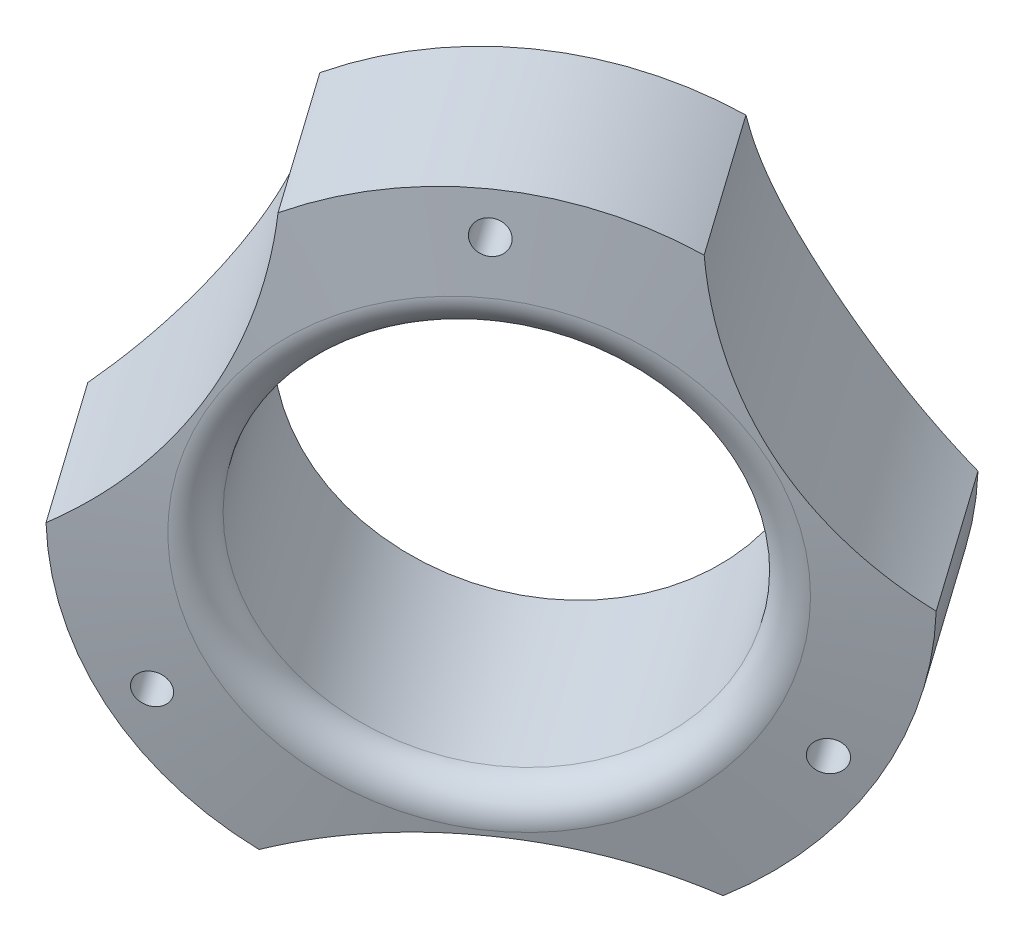
SolidWorks part; units mm, degrees
material "ABS"
ref_plane "前视基准面" through (0, 0, 0) normal (0, 0, 1) x (1, 0, 0)
ref_plane "上视基准面" through (0, 0, 0) normal (0, 1, 0) x (1, 0, 0)
ref_plane "右视基准面" through (0, 0, 0) normal (1, 0, 0) x (0, 0, -1)
other "Configuration Table"
sketch "草图1" plane through (0, 0, 0) normal (0, 1, 0) x (1, 0, 0)
  line L0 (0, 0) -> (50000, 0) construction
  line L1 (0, 0) -> (43301.2702, 25000) construction
  line L2 (0, 0) -> (25000, 43301.2702) construction
  line L3 (0, 0) -> (0, 50000) construction
  line L4 (0, 0) -> (-25000, 43301.2702) construction
  line L5 (0, 0) -> (-43301.2702, 25000) construction
  line L6 (17.4332, 10.0651) -> (35.1224, 20.2779)
  line L7 (35.1224, 20.2779) -> (22.2401, 38.5209)
  line L8 (22.2401, 38.5209) -> (11.039, 19.1201)
  line L9 (11.039, 19.1201) -> (17.4332, 10.0651)
  line L10 (29.4107, 28.3665) -> (21.242, 22.5982) construction
  line L11 (21.242, 22.5982) -> (26.426, 15.257)
  line L12 (21.242, 22.5982) -> (16.7334, 28.983)
  spline S0 degree 4 poles (4.5441, -13.9852) (5.069, -13.9115) (6.1117, -13.7144) (7.5966, -13.2868) (9.4525, -12.4738) (11.1485, -11.4611) (12.673, -10.2854) (14.0902, -8.9027) (15.2006, -7.528) (16.0517, -6.2294) (16.6357, -5.1571) (16.9969, -4.4036) (17.2795, -3.7437) (17.4701, -3.2541) (17.647, -2.7595) (17.7869, -2.3315) (17.8956, -1.9726) (17.9965, -1.6106) (18.0724, -1.3201) (18.1431, -1.0312) (18.201, -0.7763) (18.2495, -0.5466) (18.2961, -0.3139) (18.338, -0.0934) (18.3688, 0.0809) (18.404, 0.2961) (18.438, 0.517) (18.4698, 0.7375) (18.5019, 0.9839) (18.5336, 1.2626) (18.5616, 1.5443) (18.5855, 1.8273) (18.6051, 2.1103) (18.6204, 2.3933) (18.6344, 2.7474) (18.6427, 3.1726) (18.6402, 3.6687) (18.606, 4.6606) (18.4743, 6.0736) (18.1443, 7.891) (17.4882, 10.0676) (16.5951, 12.1579) (15.4804, 14.1385) (14.1536, 15.9992) (12.6297, 17.7192) (10.7951, 19.3989) (8.6272, 20.9716) (6.1287, 22.3558) (3.3088, 23.4722) (0.3713, 24.2251) (-2.6362, 24.611) (-5.6679, 24.6319) (-8.6804, 24.2953) (-11.6337, 23.6131) (-14.4905, 22.6011) (-17.8988, 20.9477) (-21.6682, 18.3857) (-25.4815, 14.66) (-28.8831, 9.6089) (-31.2279, 3.9916) (-32.5355, -2.3024) (-32.5832, -9.4982) (-30.886, -17.2942) (-27.0418, -25.1548) (-21.1423, -32.1629) (-13.78, -37.6027) (-5.394, -41.2569) (3.5764, -43.0207) (12.7127, -42.8868) (21.6333, -40.9289) (30.0036, -37.2857) (37.5425, -32.1439) (44.0239, -25.7248) (49.277, -18.2707) (53.1837, -10.0336) (55.6748, -1.2666) (56.7255, 7.7843) (56.3496, 16.8863) (54.5948, 25.8236) (51.5367, 34.4007) (47.2736, 42.4454) (41.6252, 50.2165) (33.2939, 58.6988) (21.6024, 66.7973) (6.2316, 72.9489) (-11.9297, 75.3897) (-30.1426, 73.5037) (-47.4501, 67.5662) (-63.0493, 58.0235) (-76.3038, 45.4399) (-86.7456, 30.4509) (-94.067, 13.7235) (-98.1075, -4.0757) (-98.837, -22.3066) (-96.337, -40.374) (-90.7813, -57.741) (-82.4178, -73.9383) (-71.5503, -88.568) (-58.5225, -101.306) (-43.7037, -111.9004) (-27.476, -120.169) (-10.2235, -125.9948) (7.6766, -129.3207) (25.8616, -130.1437) (43.989, -128.5088) (59.522, -125.003) (72.4202, -120.5917) (82.8104, -116.0253) (90.8771, -111.8583) (98.6697, -107.1992) (106.1617, -102.071) (114.2246, -95.801) (122.6763, -88.2215) (131.2888, -79.1727) (139.0767, -69.4058) (144.8157, -60.9536) (149.48, -53.1674) (153.2371, -46.1706) (156.1751, -40.0285) (158.8259, -33.7588) (160.8418, -28.4575) (162.3378, -24.1741) (163.5443, -20.3917) (164.5049, -17.1274) (165.2564, -14.393) (165.828, -12.1982) (166.3703, -9.9944) (166.8184, -8.0627) (167.1848, -6.398) (167.4765, -5.0161) (167.7053, -3.8925) (167.892, -2.9476) (168.0629, -2.0497) (168.1956, -1.3461) (168.4043, -0.1916) (168.4882, 0.2863) (168.6688, 1.3366) (168.7622, 1.9047) (168.8711, 2.5704) (169.0198, 3.5044) (169.1948, 4.6573) (169.389, 6.0027) (169.5701, 7.3351) (169.7422, 8.6768) (169.9433, 10.3507) (170.1641, 12.3645) (170.391, 14.7154) (170.6086, 17.4069) (170.7844, 20.1009) (170.9186, 22.7976) (171.0111, 25.4959) (171.0621, 28.1953) (171.0718, 30.8952) (171.0401, 33.595) (170.9491, 36.9686) (170.6302, 43.7113) (169.6923, 53.7988) (167.722, 65.8035) (165.138, 76.2991) (163.208, 82.7681) (162.3863, 85.3399) knots 0 0 0 0 0 0.002183 0.004365 0.006343 0.00832 0.010298 0.012275 0.014479 0.01558 0.016682 0.0173 0.017918 0.018536 0.018845 0.019463 0.019772 0.020081 0.02039 0.020699 0.021008 0.021162 0.021317 0.021626 0.021918 0.022064 0.02221 0.022501 0.022793 0.023085 0.023377 0.023669 0.023961 0.024253 0.024544 0.025128 0.025712 0.026296 0.028631 0.030966 0.033302 0.035637 0.037972 0.040307 0.042695 0.045083 0.048197 0.05131 0.054424 0.057538 0.060652 0.063766 0.066879 0.069993 0.073107 0.07622 0.082448 0.088676 0.094903 0.10113 0.107357 0.114993 0.124334 0.133675 0.143016 0.152357 0.161699 0.17104 0.18038 0.189722 0.199063 0.208404 0.217745 0.227086 0.236427 0.245769 0.25511 0.264451 0.273792 0.283133 0.292474 0.301815 0.313225 0.331907 0.35059 0.369272 0.387954 0.406636 0.425318 0.444001 0.462683 0.481365 0.500047 0.518729 0.537412 0.556094 0.574776 0.593458 0.612141 0.630823 0.649505 0.668187 0.68687 0.705552 0.724234 0.742916 0.752258 0.761599 0.77094 0.780281 0.789622 0.798963 0.812975 0.826987 0.840998 0.85034 0.85501 0.864351 0.873692 0.878363 0.883033 0.887704 0.892374 0.89471 0.897045 0.89938 0.901716 0.904051 0.905219 0.906387 0.907554 0.908722 0.909306 0.90989 0.911057 0.912447 0.912794 0.913142 0.913837 0.915226 0.916616 0.918006 0.919396 0.920785 0.922175 0.924955 0.927734 0.930513 0.933293 0.936072 0.938852 0.941631 0.944411 0.94719 0.94997 0.955529 0.972205 0.988882 1 1 1 1 1 construction
  spline S1 degree 4 poles (18.3541, 0) (18.3651, 0.0621) (18.381, 0.1554) (18.404, 0.2961) (18.438, 0.517) (18.4698, 0.7375) (18.5019, 0.9839) (18.5336, 1.2626) (18.5616, 1.5443) (18.5855, 1.8273) (18.6051, 2.1103) (18.6204, 2.3933) (18.6344, 2.7474) (18.6427, 3.1726) (18.6402, 3.6687) (18.606, 4.6606) (18.4743, 6.0736) (18.1443, 7.891) (17.4882, 10.0676) (16.5951, 12.1579) (15.4804, 14.1385) (14.1536, 15.9992) (12.6297, 17.7192) (10.7951, 19.3989) (8.6272, 20.9716) (6.1287, 22.3558) (3.3088, 23.4722) (0.3713, 24.2251) (-2.6362, 24.611) (-5.6679, 24.6319) (-8.6804, 24.2953) (-11.6337, 23.6131) (-14.4905, 22.6011) (-17.8988, 20.9477) (-21.6682, 18.3857) (-25.4815, 14.66) (-28.8831, 9.6089) (-31.2279, 3.9916) (-32.5355, -2.3024) (-32.5832, -9.4982) (-30.886, -17.2942) (-27.0418, -25.1548) (-21.1423, -32.1629) (-13.78, -37.6027) (-5.394, -41.2569) (3.5764, -43.0207) (12.7127, -42.8868) (21.6333, -40.9289) (30.0036, -37.2857) (37.5425, -32.1439) (44.0239, -25.7248) (49.277, -18.2707) (53.1837, -10.0336) (55.6748, -1.2666) (56.7255, 7.7843) (56.3496, 16.8863) (54.5948, 25.8236) (51.5367, 34.4007) (47.2736, 42.4454) (41.6252, 50.2165) (33.2939, 58.6988) (21.6024, 66.7973) (6.2316, 72.9489) (-11.9297, 75.3897) (-30.1426, 73.5037) (-47.4501, 67.5662) (-63.0493, 58.0235) (-76.3038, 45.4399) (-86.7456, 30.4509) (-94.067, 13.7235) (-98.1075, -4.0757) (-98.837, -22.3066) (-96.337, -40.374) (-90.7813, -57.741) (-82.4178, -73.9383) (-71.5503, -88.568) (-58.5225, -101.306) (-43.7037, -111.9004) (-27.476, -120.169) (-10.2235, -125.9948) (7.6766, -129.3207) (25.8616, -130.1437) (43.989, -128.5088) (59.522, -125.003) (72.4202, -120.5917) (82.8104, -116.0253) (90.8771, -111.8583) (98.6697, -107.1992) (106.1617, -102.071) (114.2246, -95.801) (122.6763, -88.2215) (131.2888, -79.1727) (139.0767, -69.4058) (144.8157, -60.9536) (149.48, -53.1674) (153.2371, -46.1706) (156.1751, -40.0285) (158.8259, -33.7588) (160.8418, -28.4575) (162.3378, -24.1741) (163.5443, -20.3917) (164.5049, -17.1274) (165.2564, -14.393) (165.828, -12.1982) (166.3703, -9.9944) (166.8184, -8.0627) (167.1848, -6.398) (167.4765, -5.0161) (167.7053, -3.8925) (167.892, -2.9476) (168.0629, -2.0497) (168.1956, -1.3461) (168.3264, -0.6223) (168.3933, -0.2484) (168.4372, 0) knots 0.021626 0.021626 0.021626 0.021626 0.021626 0.021918 0.022064 0.02221 0.022501 0.022793 0.023085 0.023377 0.023669 0.023961 0.024253 0.024544 0.025128 0.025712 0.026296 0.028631 0.030966 0.033302 0.035637 0.037972 0.040307 0.042695 0.045083 0.048197 0.05131 0.054424 0.057538 0.060652 0.063766 0.066879 0.069993 0.073107 0.07622 0.082448 0.088676 0.094903 0.10113 0.107357 0.114993 0.124334 0.133675 0.143016 0.152357 0.161699 0.17104 0.18038 0.189722 0.199063 0.208404 0.217745 0.227086 0.236427 0.245769 0.25511 0.264451 0.273792 0.283133 0.292474 0.301815 0.313225 0.331907 0.35059 0.369272 0.387954 0.406636 0.425318 0.444001 0.462683 0.481365 0.500047 0.518729 0.537412 0.556094 0.574776 0.593458 0.612141 0.630823 0.649505 0.668187 0.68687 0.705552 0.724234 0.742916 0.752258 0.761599 0.77094 0.780281 0.789622 0.798963 0.812975 0.826987 0.840998 0.85034 0.85501 0.864351 0.873692 0.878363 0.883033 0.887704 0.892374 0.89471 0.897045 0.89938 0.901716 0.904051 0.905219 0.906387 0.907554 0.908722 0.909306 0.90989 0.911057 0.911057 0.911057 0.911057 0.911057
  spline S2 degree 4 poles (26.7771, -19.4547) (27.2791, -18.9699) (28.2564, -17.9726) (29.6389, -16.3972) (31.5138, -13.8737) (32.9647, -11.4834) (34.0651, -9.2997) (34.8847, -7.3726) (35.3191, -6.2309) (35.6599, -5.2409) (35.9229, -4.4091) (36.0959, -3.8235) (36.2363, -3.3192) (36.3702, -2.8132) (36.4765, -2.3905) (36.5777, -1.9654) (36.6735, -1.5395) (36.7371, -1.2443) (36.7899, -0.9895) (36.8338, -0.7701) (36.8689, -0.5895) (36.9122, -0.3614) (36.9643, -0.079) (37.0022, 0.137) (37.056, 0.4587) (37.1012, 0.7414) (37.1347, 0.96) (37.1737, 1.2255) (37.2176, 1.5413) (37.2661, 1.9157) (37.3168, 2.3441) (37.3624, 2.7721) (37.4134, 3.3079) (37.4649, 3.9519) (37.524, 4.9191) (37.5642, 6.2107) (37.5499, 8.58) (37.2749, 12.0191) (36.4953, 16.2666) (34.9181, 21.2024) (32.7382, 25.9024) (30.2297, 29.9345) (27.5748, 33.3344) (24.3272, 36.7897) (20.4102, 40.1789) (15.3713, 43.5302) (9.113, 46.471) (2.4988, 48.4837) (-3.4771, 49.4179) (-8.6498, 49.6296) (-15.5372, 49.2939) (-22.3494, 48.0444) (-29.7217, 45.4984) (-37.3047, 41.3681) (-42.9225, 37.3494) (-49.2948, 31.5248) (-55.7813, 23.4083) (-61.4472, 12.6507) (-65.4181, -1.9048) (-66.0143, -20.496) (-61.2011, -38.6277) (-51.6663, -54.6681) (-39.5267, -67.0168) (-28.241, -75.0457) (-15.7631, -81.0448) (-2.4709, -84.9081) (11.2641, -86.5959) (25.0917, -86.1269) (38.6859, -83.5703) (51.7521, -79.0376) (62.4941, -73.4702) (71.0671, -67.6624) (77.7289, -62.1925) (82.7475, -57.4634) (87.4361, -52.4071) (91.7776, -47.05) (95.7571, -41.4188) (99.3618, -35.5409) (102.1786, -30.2056) (104.3465, -25.5122) (105.8226, -21.9278) (106.7439, -19.5134) (107.4694, -17.486) (108.0246, -15.8552) (108.5543, -14.216) (109.0585, -12.5687) (109.5372, -10.914) (109.9904, -9.2519) (110.418, -7.5833) (110.7697, -6.1172) (111.0551, -4.8577) (111.2824, -3.8044) (111.4574, -2.9629) (111.6056, -2.2213) (111.7181, -1.6396) (111.7961, -1.2276) (111.8764, -0.7956) (111.9824, -0.2107) (112.0406, 0.1173) (112.149, 0.7476) (112.2197, 1.1704) (112.2736, 1.499) (112.3401, 1.912) (112.4454, 2.5814) (112.5829, 3.4978) (112.7468, 4.6683) (112.9181, 6.007) (113.1127, 7.6834) (113.3147, 9.6981) (113.5046, 12.0531) (113.6588, 14.7487) (113.7504, 17.4473) (113.7796, 20.1472) (113.7303, 24.197) (113.4243, 30.2662) (112.8255, 35.6383) (112.057, 40.3021) (111.5392, 42.9519) knots 0 0 0 0 0 0.005611 0.011222 0.016833 0.02525 0.028055 0.030861 0.033666 0.035069 0.036472 0.037875 0.038576 0.039277 0.04068 0.041381 0.042083 0.042784 0.043135 0.043486 0.043836 0.044187 0.044888 0.045754 0.046187 0.04662 0.047052 0.047485 0.048351 0.049216 0.050082 0.050948 0.051813 0.053545 0.055276 0.058738 0.062201 0.072588 0.082976 0.093363 0.103751 0.114138 0.121063 0.127988 0.141838 0.155688 0.169538 0.183388 0.197238 0.204163 0.211088 0.238788 0.252638 0.266488 0.280339 0.294189 0.321888 0.349589 0.377289 0.414571 0.469971 0.497671 0.525371 0.553071 0.580771 0.608471 0.636171 0.663871 0.691571 0.719271 0.746971 0.760821 0.774671 0.788521 0.802371 0.816222 0.830072 0.843922 0.857772 0.864697 0.871622 0.875084 0.878547 0.882009 0.885472 0.888934 0.892397 0.895859 0.899322 0.902784 0.904515 0.906247 0.907978 0.909709 0.910575 0.911008 0.91144 0.913172 0.914528 0.915207 0.915885 0.916563 0.917242 0.918599 0.921312 0.924025 0.926739 0.929452 0.934879 0.940306 0.945732 0.951159 0.956586 0.962013 0.978293 1 1 1 1 1 construction
  spline S3 degree 4 poles (36.9778, 0) (36.994, 0.0921) (37.0177, 0.2297) (37.056, 0.4587) (37.1012, 0.7414) (37.1347, 0.96) (37.1737, 1.2255) (37.2176, 1.5413) (37.2661, 1.9157) (37.3168, 2.3441) (37.3624, 2.7721) (37.4134, 3.3079) (37.4649, 3.9519) (37.524, 4.9191) (37.5642, 6.2107) (37.5499, 8.58) (37.2749, 12.0191) (36.4953, 16.2666) (34.9181, 21.2024) (32.7382, 25.9024) (30.2297, 29.9345) (27.5748, 33.3344) (24.3272, 36.7897) (20.4102, 40.1789) (15.3713, 43.5302) (9.113, 46.471) (2.4988, 48.4837) (-3.4771, 49.4179) (-8.6498, 49.6296) (-15.5372, 49.2939) (-22.3494, 48.0444) (-29.7217, 45.4984) (-37.3047, 41.3681) (-42.9225, 37.3494) (-49.2948, 31.5248) (-55.7813, 23.4083) (-61.4472, 12.6507) (-65.4181, -1.9048) (-66.0143, -20.496) (-61.2011, -38.6277) (-51.6663, -54.6681) (-39.5267, -67.0168) (-28.241, -75.0457) (-15.7631, -81.0448) (-2.4709, -84.9081) (11.2641, -86.5959) (25.0917, -86.1269) (38.6859, -83.5703) (51.7521, -79.0376) (62.4941, -73.4702) (71.0671, -67.6624) (77.7289, -62.1925) (82.7475, -57.4634) (87.4361, -52.4071) (91.7776, -47.05) (95.7571, -41.4188) (99.3618, -35.5409) (102.1786, -30.2056) (104.3465, -25.5122) (105.8226, -21.9278) (106.7439, -19.5134) (107.4694, -17.486) (108.0246, -15.8552) (108.5543, -14.216) (109.0585, -12.5687) (109.5372, -10.914) (109.9904, -9.2519) (110.418, -7.5833) (110.7697, -6.1172) (111.0551, -4.8577) (111.2824, -3.8044) (111.4574, -2.9629) (111.6056, -2.2213) (111.7181, -1.6396) (111.7961, -1.2276) (111.8764, -0.7956) (111.946, -0.4114) (111.9868, -0.1841) (112.0193, 0) knots 0.044888 0.044888 0.044888 0.044888 0.044888 0.045754 0.046187 0.04662 0.047052 0.047485 0.048351 0.049216 0.050082 0.050948 0.051813 0.053545 0.055276 0.058738 0.062201 0.072588 0.082976 0.093363 0.103751 0.114138 0.121063 0.127988 0.141838 0.155688 0.169538 0.183388 0.197238 0.204163 0.211088 0.238788 0.252638 0.266488 0.280339 0.294189 0.321888 0.349589 0.377289 0.414571 0.469971 0.497671 0.525371 0.553071 0.580771 0.608471 0.636171 0.663871 0.691571 0.719271 0.746971 0.760821 0.774671 0.788521 0.802371 0.816222 0.830072 0.843922 0.857772 0.864697 0.871622 0.875084 0.878547 0.882009 0.885472 0.888934 0.892397 0.895859 0.899322 0.902784 0.904515 0.906247 0.907978 0.909709 0.910575 0.911008 0.91144 0.913172 0.913172 0.913172 0.913172 0.913172
  point P29 (21.242, 22.5982)
  dimension "D1" = 10
revolve "旋转1" add sketch "草图1" angle 360 about L7 region at (18.302, 0, -18.7643) region at (14.4849, 0, -14.7468)
ref_plane "基准面2" through (1.6038, 0, 2.2712) normal (0.5768, 0, 0.8169) x (0.8169, 0, -0.5768)
sketch "草图2" plane through (1.6038, 0, 2.2712) normal (0.5768, 0, 0.8169) x (0.8169, 0, -0.5768)
  line L0 (40.3871, 20.3408) -> (40.3871, 17.8408) construction
  line L1 (40.3871, 0) -> (12.899, 0) construction
  line L2 (40.3871, 0) -> (5.7461, 20) construction
  circle A0 centre (40.3871, 0) radius 20.3408 construction
  circle A1 centre (40.3871, 17.8408) radius 1
  circle A2 centre (5.7461, 20) radius 25
  circle A3 centre (75.0282, 20) radius 25
  circle A4 centre (55.8377, -8.9204) radius 1
  circle A5 centre (40.3871, -40) radius 25
  circle A6 centre (24.9366, -8.9204) radius 1
  circle A7 centre (40.3871, 0) radius 12.5
  point P6 (40.3871, 0)
  dimension "D2" = 2
  dimension "D4" = 50
  dimension "D6" = 25
  dimension "D1" = 2.5
  dimension "D3" = 30
  dimension "D5" = 3
extrude "切除-拉伸1" cut sketch "草图2" against normal blind 24 contours A2 | A3 | A5 | A1 | A6 | A4 | A7 region at (34.5946, 17.8408, -21.0253) region at (6.2976, 20, -1.0434) region at (62.8916, 20, -41.0073) region at (47.2156, -8.9204, -29.9377) region at (34.5946, -40, -21.0253) region at (21.9736, -8.9204, -12.113) region at (34.5946, 0, -21.0253)
fillet "圆角1" radius 2 1 edges at (24.2519, 0, -14.0018)
